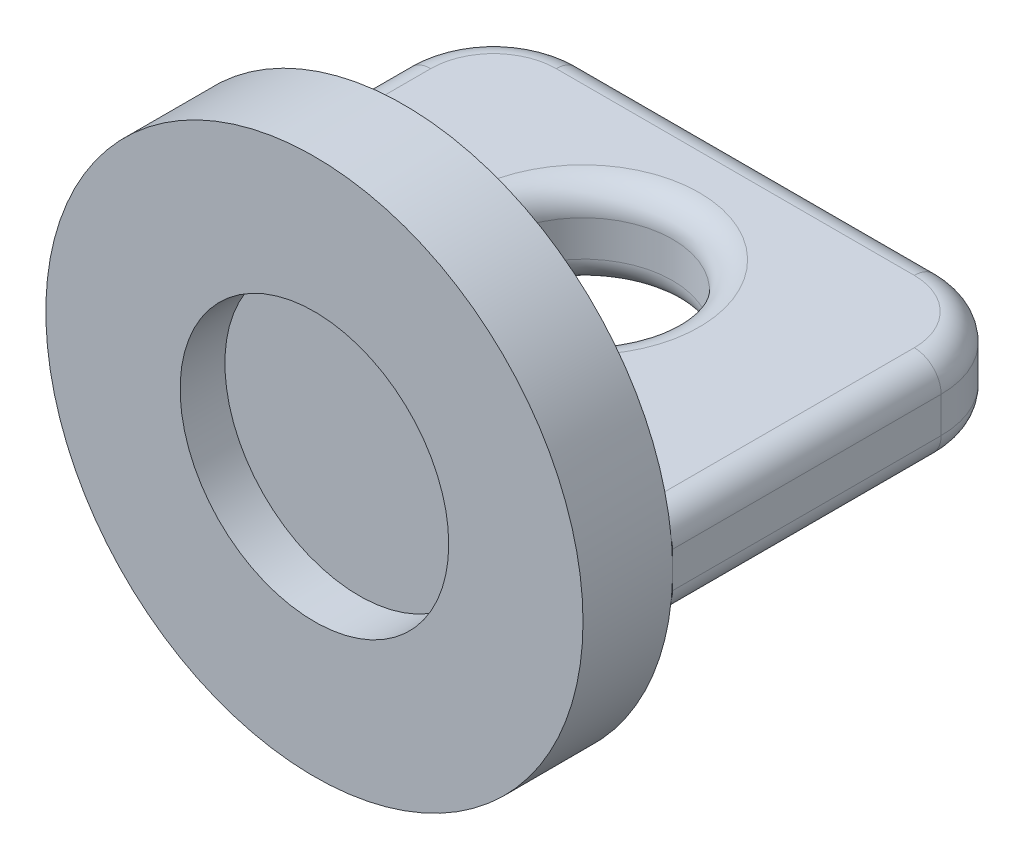
SolidWorks part; units mm, degrees
ref_plane "Alzado" through (0, 0, 0) normal (0, 0, 1) x (1, 0, 0)
ref_plane "Planta" through (0, 0, 0) normal (0, 1, 0) x (1, 0, 0)
ref_plane "Vista lateral" through (0, 0, 0) normal (1, 0, 0) x (0, 0, -1)
sketch "Croquis1" plane through (0, 0, 0) normal (0, 0, 1) x (1, 0, 0)
  circle A0 centre (0, 0) radius 30
  dimension "D1" = 60
extrude "Saliente-Extruir1" add sketch "Croquis1" along normal blind 10
sketch "Croquis2" plane through (0, 0, 0) normal (0, 1, 0) x (1, 0, 0)
  line L0 (30, -10) -> (30, 0) construction
  line L1 (-30, 0) -> (30, 0)
  line L2 (-30, 0) -> (-30, 40)
  line L3 (-30, 40) -> (30, 40)
  line L4 (30, 0) -> (30, 40)
  dimension "D1" = 40
extrude "Saliente-Extruir2" add sketch "Croquis2" along normal mid plane 10
fillet "Redondeo1" radius 10 2 edges at (30, 0, -40) (-30, 0, -40)
fillet "Redondeo2" radius 3 10 edges at (30, -5, -15) (27.0711, -5, -37.0711) (-30, -5, -15) (-27.0711, -5, -37.0711) (30, 5, -15) (27.0711, 5, -37.0711) (-30, 5, -15) (-27.0711, 5, -37.0711) (0, -5, -40) (0, 5, -40)
sketch "Croquis3" plane through (0, 0, 10) normal (0, 0, 1) x (1, 0, 0)
  circle A0 centre (0, 0) radius 15
  dimension "D1" = 30
extrude "Cortar-Extruir1" cut sketch "Croquis3" against normal blind 5
sketch "Croquis4" plane through (0, -5, 0) normal (0, -1, 0) x (1, 0, 0)
  line L0 (0, 0) -> (0, -40) construction
  line L1 (20, -40) -> (-20, -40) construction
  circle A0 centre (0, -20) radius 10
  point P7 (0, -20)
  dimension "D1" = 20
extrude "Cortar-Extruir2" cut sketch "Croquis4" against normal through all
fillet "Redondeo3" radius 3 2 edges at (0, 5, -30) (0, -5, -30)
